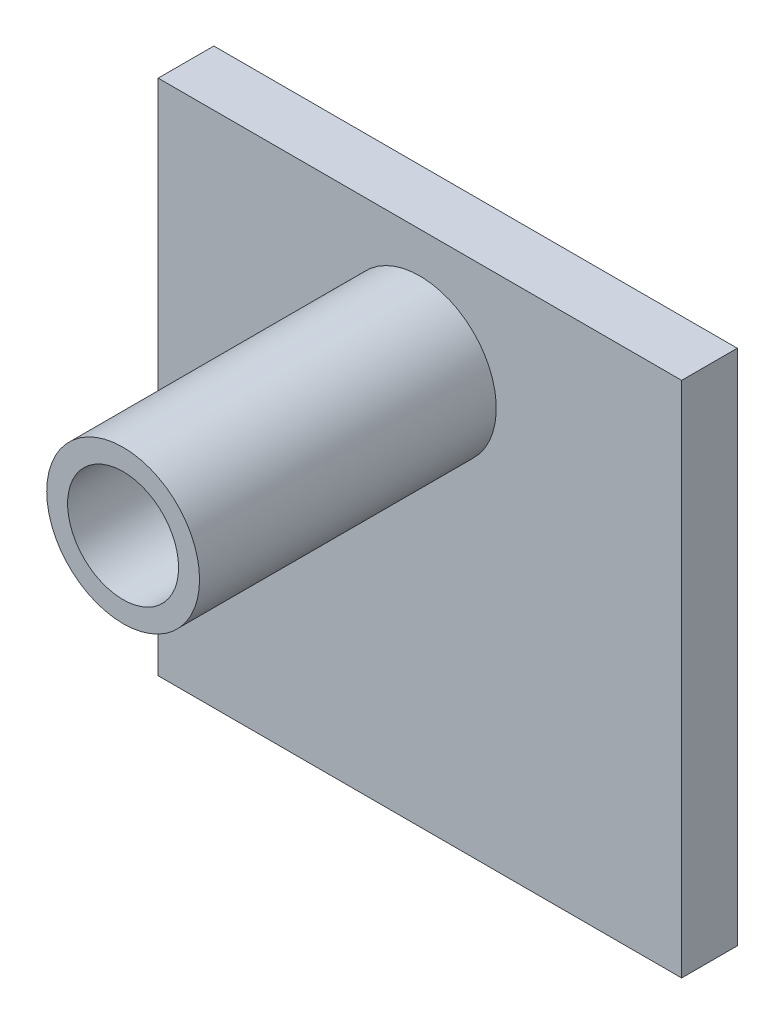
SolidWorks part; units mm, degrees
ref_plane "前视基准面" through (0, 0, 0) normal (0, 0, 1) x (1, 0, 0)
ref_plane "上视基准面" through (0, 0, 0) normal (0, 1, 0) x (1, 0, 0)
ref_plane "右视基准面" through (0, 0, 0) normal (1, 0, 0) x (0, 0, -1)
sketch "草图1" plane through (0, 0, 0) normal (0, 0, 1) x (1, 0, 0)
  line L1 (-28.2258, -27.9097) -> (28.2258, -27.9097)
  line L2 (-28.2258, -27.9097) -> (-28.2258, 27.9097)
  line L3 (-28.2258, 27.9097) -> (28.2258, 27.9097)
  line L4 (28.2258, -27.9097) -> (28.2258, 27.9097)
  line L5 (-28.2258, -27.9097) -> (28.2258, 27.9097) construction
  line L6 (-28.2258, 27.9097) -> (28.2258, -27.9097) construction
  circle A0 centre (0, 15.269) radius 6.0082
  point P0 (0, 0)
extrude "凸台-拉伸1" add sketch "草图1" along normal blind 6
sketch "草图2" plane through (0, 0, 6) normal (0, 0, 1) x (1, 0, 0)
  circle A2 centre (-0.012, 15.2899) radius 5.9841
extrude "凸台-拉伸2" add sketch "草图2" along normal blind 32 separate body
sketch "草图3" plane through (0, 0, 6) normal (0, 0, 1) x (1, 0, 0)
  circle A0 centre (-0.0067, 15.3033) radius 8.2405
extrude "凸台-拉伸3" add sketch "草图3" along normal blind 32
extrude "切除-拉伸2" cut sketch "草图2<3>" along normal through all
sketch "草图2<3>" plane through (0, 0, 6) normal (0, 0, 1) x (1, 0, 0) same geometry as "草图2"
